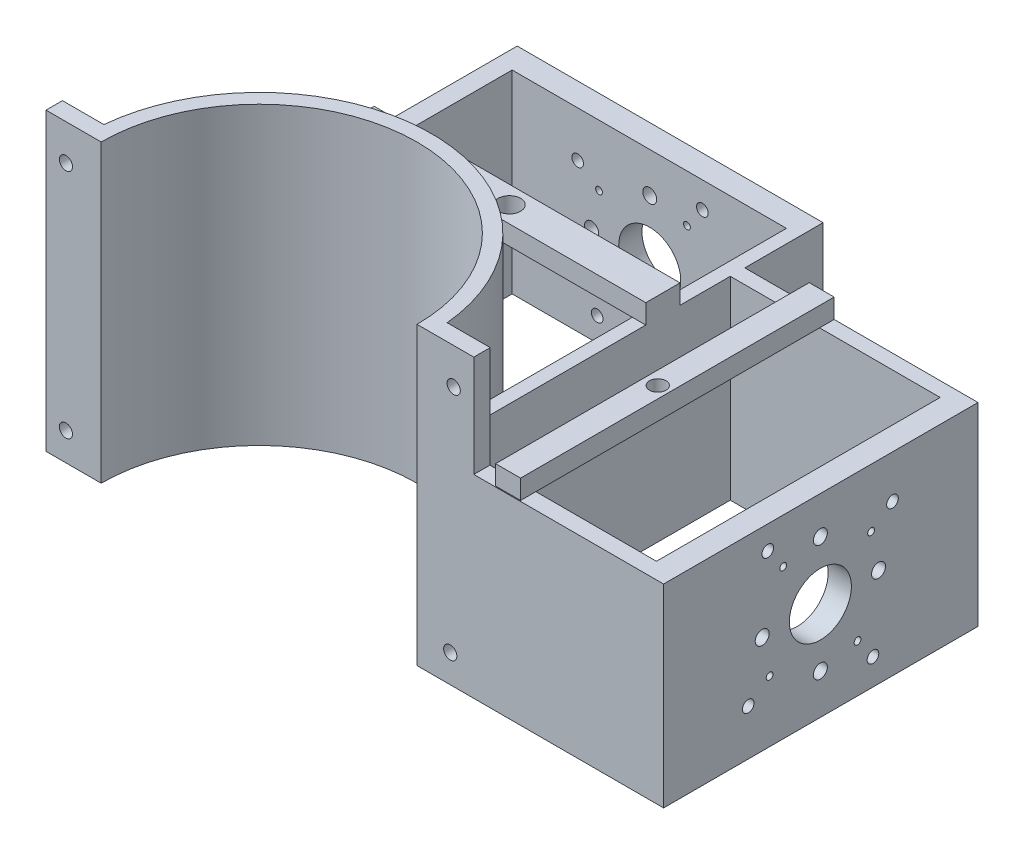
SolidWorks part; units mm, degrees
note: The reader was unsure of these and kept them because the rebuilt part matched: shared geometry of "Sketch8<3>".
ref_plane "Front Plane" through (0, 0, 0) normal (0, 0, 1) x (1, 0, 0)
ref_plane "Top Plane" through (0, 0, 0) normal (0, 1, 0) x (1, 0, 0)
ref_plane "Right Plane" through (0, 0, 0) normal (1, 0, 0) x (0, 0, -1)
sketch "Sketch1" plane through (0, 0, 0) normal (0, 1, 0) x (1, 0, 0)
  line L0 (-44.45, 0) -> (44.45, 0)
  line L2 (-40.7168, 0) -> (-54.9362, 0)
  line L3 (-40.7168, 0) -> (-40.7168, 4.2412)
  line L4 (-40.7168, 4.2412) -> (-54.9362, 4.2412)
  line L5 (-54.9362, 0) -> (-54.9362, 4.2412)
  line L6 (40.7168, 0) -> (55.3596, 0)
  line L7 (40.7168, 0) -> (40.7168, 4.2412)
  line L8 (40.7168, 4.2412) -> (55.3596, 4.2412)
  line L9 (55.3596, 0) -> (55.3596, 4.2412)
  circle A0 centre (0, 0) radius 44.45
  circle A1 centre (0, 0) radius 40.7168
extrude "Boss-Extrude1" add sketch "Sketch1" along normal blind 76.2 contours A1 L7 L8 A0 L4 L3 | L4 A0 L0 L3 | A0 L4 L5 L2 | L0 A0 L8 L7
sketch "Sketch2" plane through (0, 0, -4.2412) normal (0, 0, -1) x (-1, 0, 0)
  circle A0 centre (-49.2914, 7.2315) radius 1.5
  circle A1 centre (-50.1719, 66.9454) radius 1.5
  circle A2 centre (49.8049, 66.9454) radius 1.5
  circle A3 centre (49.8049, 7.2315) radius 1.5
hole_wizard "M3 Clearance Hole1" positions "3DSketch1" profile "Sketch3" hole size "M3" standard "ANSI Metric" end condition through all
sketch3d "3DSketch1"
  point P0 (50.1719, 66.9454, -4.2412)
  point P3 (49.2914, 7.2315, -4.2412)
  point P6 (-49.8049, 7.2315, -4.2412)
  point P9 (-49.8049, 66.9454, -4.2412)
sketch "Sketch3" plane through (50.1719, 66.9454, -4.2412) normal (1, 0, 0) x (0, 1, 0)
  line L0 (0, 0) -> (0, 4.2412)
  line L1 (0, 4.2412) -> (1.7, 4.2412)
  line L2 (1.7, 4.2412) -> (1.7, 0.025)
  line L3 (1.7, 0.025) -> (1.725, 0)
  line L5 (1.725, 0) -> (0, 0)
  line L6 (-1.7, 0.025) -> (-1.725, 0) construction
  line L11 (0, -6.35) -> (0, 107.95) construction
  dimension "Thru Hole Dia." = 3.4
  dimension "Thru Hole Depth" = 4.2412
  dimension "Near C'Sink Dia." = 3.45
  dimension "Near C'Sink Angle" = 90
sketch "Sketch5" plane through (0, 0, 0) normal (0, -1, 0) x (1, 0, 0)
  line L0 (0, -44.45) -> (0, -95.25) construction
  line L1 (0, -44.45) -> (-30, -44.45) construction
  line L2 (0, -44.45) -> (30, -44.45) construction
  line L4 (-30, -27.5293) -> (-34.6976, -27.5293)
  line L5 (-30, -27.5293) -> (-30, -95.25)
  line L6 (-30, -95.25) -> (-34.6976, -95.25)
  line L7 (-34.6976, -27.5293) -> (-34.6976, -95.25)
  line L12 (-34.6976, -95.25) -> (44.1739, -95.25)
  line L13 (-34.6976, -95.25) -> (-34.6976, -101.25)
  line L14 (-34.6976, -101.25) -> (44.1739, -101.25)
  line L15 (44.1739, -95.25) -> (44.1739, -101.25)
  line L20 (44.1739, -95.25) -> (40.7168, -95.25)
  line L21 (44.1739, -95.25) -> (44.1739, 0)
  line L22 (44.1739, 0) -> (40.7168, 0)
  line L23 (40.7168, -95.25) -> (40.7168, 0)
  arc A0 (-44.2472, -4.2412) -> (44.2472, -4.2412) centre (0, 0) ccw construction
  arc A1 (-40.7168, 0) -> (40.7168, 0) centre (0, 0) ccw construction
extrude "Boss-Extrude2" add sketch "Sketch5" against normal blind 50
sketch "Sketch6" plane through (0, 0, -101.25) normal (0, 0, -1) x (-1, 0, 0)
  circle A0 centre (-5.4745, 24.6225) radius 15.0724 construction
  circle A1 centre (-5.4745, 24.6225) radius 8
  circle A2 centre (-5.4745, 24.6225) radius 16.2803 construction
  circle A3 centre (-15.0663, 37.7772) radius 0.875
  circle A4 centre (7.6046, 34.2834) radius 0.875
  circle A5 centre (4.1109, 11.6125) radius 0.875
  circle A6 centre (-18.56, 15.1063) radius 0.875
  circle A7 centre (-5.4745, 39.6949) radius 1.8
  circle A8 centre (9.5223, 24.6917) radius 1.8
  circle A9 centre (-5.4809, 9.6949) radius 1.8
  circle A10 centre (-20.4777, 24.6981) radius 1.8
  circle A11 centre (-5.4745, 24.6225) radius 23.0704
  circle A12 centre (-19.0376, 43.2849) radius 1.5
  circle A13 centre (13.1123, 38.2548) radius 1.5
  circle A14 centre (8.0822, 6.1048) radius 1.5
  circle A15 centre (-24.0677, 11.1349) radius 1.5
  circle A16 centre (-5.4745, 24.6225) radius 30
  point P15 (-5.4777, 24.6949)
  point P24 (-5.4777, 24.6949)
  point P34 (-5.4777, 24.6949)
  dimension "D1" = 4
  dimension "D2" = 4
  dimension "D3" = 4
extrude "Cut-Extrude1" cut sketch "Sketch6" against normal up to next contours A15 | A14 | A13 | A12 | A7 | A3 | A8 | A5 | A9 | A10 | A6 | A1 | A4
sketch "Sketch8" plane through (0, 0, 0) normal (0, -1, 0) x (1, 0, 0)
  line L0 (40.7168, -95.25) -> (40.7168, -17.8309) construction
  line L2 (98.2908, -17.3091) -> (98.2908, -77.3091) construction
  line L3 (98.2908, -77.3091) -> (40.7168, -77.3091)
  line L4 (40.7168, 0) -> (98.2908, 0)
  line L5 (40.7168, 0) -> (40.7168, -4.159)
  line L6 (40.7168, -4.159) -> (98.2908, -4.159)
  line L7 (98.2908, 0) -> (98.2908, -4.159)
  line L12 (98.2908, 0) -> (104.2908, 0)
  line L13 (98.2908, 0) -> (98.2908, -81.0646)
  line L14 (98.2908, -81.0646) -> (104.2908, -81.0646)
  line L15 (104.2908, 0) -> (104.2908, -81.0646)
  line L16 (98.2908, -77.3091) -> (98.2908, -81.0646)
  line L17 (98.2908, -81.0646) -> (40.7168, -81.0646)
  line L18 (40.7168, -77.3091) -> (40.7168, -81.0646)
extrude "Boss-Extrude4" add sketch "Sketch8" against normal blind 50
extrude "Boss-Extrude5" add sketch "Sketch8<3>" against normal blind 50 contours L15 L12 L7 L13 L16 L14
sketch "Sketch8<3>" plane through (0, 0, 0) normal (0, -1, 0) x (1, 0, 0) same geometry as "Sketch8"
sketch "Sketch9" plane through (104.2908, 0, 0) normal (1, 0, 0) x (0, 0, -1)
  circle A0 centre (40.4266, 25.2901) radius 15.0724 construction
  circle A1 centre (40.4266, 25.2901) radius 8
  circle A2 centre (40.4266, 25.2901) radius 16.2803 construction
  circle A3 centre (30.8348, 38.4448) radius 0.875
  circle A4 centre (53.5057, 34.9511) radius 0.875
  circle A5 centre (50.0119, 12.2802) radius 0.875
  circle A6 centre (27.341, 15.7739) radius 0.875
  circle A7 centre (40.4266, 40.3625) radius 1.8
  circle A8 centre (55.4234, 25.3593) radius 1.8
  circle A9 centre (40.4201, 10.3625) radius 1.8
  circle A10 centre (25.4234, 25.3657) radius 1.8
  circle A11 centre (40.4266, 25.2901) radius 23.0704
  circle A12 centre (26.8634, 43.9525) radius 1.5
  circle A13 centre (59.0134, 38.9224) radius 1.5
  circle A14 centre (53.9833, 6.7725) radius 1.5
  circle A15 centre (21.8333, 11.8026) radius 1.5
  circle A16 centre (40.4266, 25.2901) radius 30
  point P15 (40.4234, 25.3625)
  point P24 (40.4234, 25.3625)
  point P31 (40.4234, 25.3625)
extrude "Cut-Extrude2" cut sketch "Sketch9" against normal up to next contours A1 | A13 | A8 | A4 | A7 | A3 | A12 | A10 | A6 | A9 | A5 | A14 | A15
sketch "Sketch11" plane through (0, 50, 0) normal (0, 1, 0) x (1, 0, 0)
  line L0 (-34.6976, 27.7827) -> (-34.6976, 101.25) construction
  line L1 (-34.6976, 64.3653) -> (44.1739, 64.3653)
  line L2 (-34.6976, 64.3653) -> (-34.6976, 55.5322)
  line L3 (-34.6976, 55.5322) -> (44.1739, 55.5322)
  line L4 (44.1739, 64.3653) -> (44.1739, 55.5322)
  line L5 (44.1739, 4.9468) -> (44.1739, 77.3091) construction
  circle A0 centre (4.7381, 59.7852) radius 2.899
  point P10 (4.7381, 59.7852)
extrude "Boss-Extrude6" add sketch "Sketch11" along normal blind 5
sketch "Sketch13" plane through (0, 50, 0) normal (0, 1, 0) x (1, 0, 0)
  line L0 (104.2908, 81.0646) -> (44.1739, 81.0646) construction
  line L1 (60.7673, 81.0646) -> (67.2024, 81.0646)
  line L2 (60.7673, 81.0646) -> (60.7673, 0.2182)
  line L3 (60.7673, 0.2182) -> (67.2024, 0.2182)
  line L4 (67.2024, 81.0646) -> (67.2024, 0.2182)
  circle A0 centre (64.2092, 38.5797) radius 2.1265
  point P6 (64.2092, 38.5797)
extrude "Boss-Extrude9" add sketch "Sketch13" along normal blind 5
